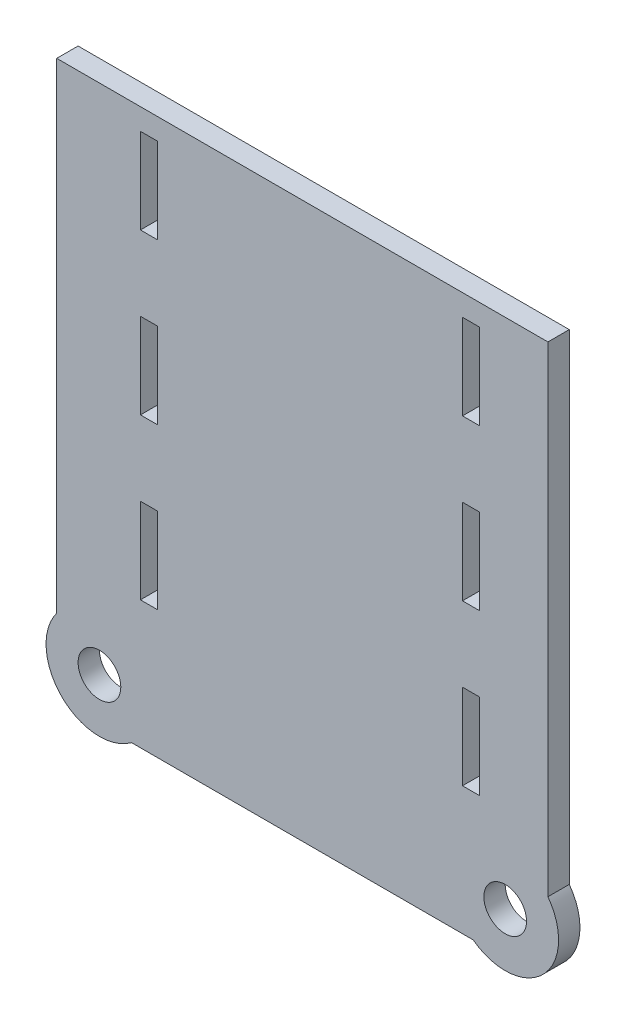
SolidWorks part; units mm, degrees
ref_plane "Front Plane" through (0, 0, 0) normal (0, 0, 1) x (1, 0, 0)
ref_plane "Top Plane" through (0, 0, 0) normal (0, 1, 0) x (1, 0, 0)
ref_plane "Right Plane" through (0, 0, 0) normal (1, 0, 0) x (0, 0, -1)
sketch "Sketch1" plane through (0, 0, 0) normal (0, 0, 1) x (1, 0, 0)
  line L0 (0, 0) -> (0, 152.4) construction
  line L1 (0.0027, -12.7) -> (-50.8, -12.7)
  line L2 (-73.025, 9.525) -> (-73.025, 152.4)
  line L3 (-73.025, 152.4) -> (73.025, 152.4)
  line L4 (73.025, 9.525) -> (73.025, 152.4)
  line L5 (-0.0027, -12.7) -> (50.8, -12.7)
  circle A0 centre (-60.325, 0) radius 6.35
  arc A1 (-73.025, 9.525) -> (-50.8, -12.7) centre (-60.325, 0) ccw
  arc A2 (73.025, 9.525) -> (50.8, -12.7) centre (60.325, 0) cw
  circle A3 centre (60.325, 0) radius 6.35
  dimension "D1" = 12.7
  dimension "D2" = 31.75
  dimension "D3" = 60.325
  dimension "D4" = 146.05
  dimension "D5" = 12.7
  dimension "D6" = 152.4
extrude "Boss-Extrude1" add sketch "Sketch1" along normal mid plane 6.35 contours A2 L4 L3 L2 A1 L1 L5 A0 A3 region at (0, 70.0905, 0)
sketch "Sketch2" plane through (0, 0, 3.175) normal (0, 0, 1) x (1, 0, 0)
  line L0 (-43.053, 152.4) -> (-43.053, -12.7) construction
  line L1 (-73.025, 152.4) -> (73.025, 152.4) construction
  line L2 (50.8, -12.7) -> (-50.8, -12.7) construction
  line L3 (47.625, 152.4) -> (47.625, -12.7) construction
  line L4 (73.025, 9.525) -> (73.025, 152.4) construction
  line L5 (-73.025, 9.525) -> (-73.025, 152.4) construction
  line L6 (-45.593, 120.65) -> (-45.593, 98.425) construction
  line L7 (-48.133, 146.05) -> (-43.053, 146.05)
  line L8 (-48.133, 146.05) -> (-48.133, 120.65)
  line L9 (-48.133, 120.65) -> (-43.053, 120.65)
  line L10 (-43.053, 146.05) -> (-43.053, 120.65)
  line L11 (-48.133, 98.425) -> (-43.053, 98.425)
  line L12 (-48.133, 98.425) -> (-48.133, 73.025)
  line L13 (-48.133, 73.025) -> (-43.053, 73.025)
  line L14 (-43.053, 98.425) -> (-43.053, 73.025)
  line L15 (-48.133, 50.8) -> (-43.053, 50.8)
  line L16 (-48.133, 50.8) -> (-48.133, 25.4)
  line L17 (-48.133, 25.4) -> (-43.053, 25.4)
  line L18 (-43.053, 50.8) -> (-43.053, 25.4)
  line L19 (-45.593, 73.025) -> (-45.593, 50.8) construction
  line L20 (47.625, 120.65) -> (52.705, 120.65)
  line L21 (52.705, 50.8) -> (52.705, 25.4)
  line L22 (47.625, 146.05) -> (52.705, 146.05)
  line L23 (47.625, 73.025) -> (52.705, 73.025)
  line L24 (47.625, 98.425) -> (47.625, 73.025)
  line L25 (47.625, 98.425) -> (52.705, 98.425)
  line L26 (52.705, 152.4) -> (52.705, -13.9266) construction
  line L27 (47.625, 50.8) -> (47.625, 25.4)
  line L28 (47.625, 25.4) -> (52.705, 25.4)
  line L29 (50.165, 120.65) -> (50.165, 98.425) construction
  line L30 (52.705, 98.425) -> (52.705, 73.025)
  line L31 (52.705, 146.05) -> (52.705, 120.65)
  line L32 (47.625, 146.05) -> (47.625, 120.65)
  line L33 (47.625, 50.8) -> (52.705, 50.8)
  line L34 (50.165, 73.025) -> (50.165, 50.8) construction
  arc A0 (50.8, -12.7) -> (73.025, 9.525) centre (60.325, 0) ccw construction
  point P46 (52.4631, 152.4)
  point P47 (21.0966, 148.0911)
  point P48 (0, 0)
  point P49 (52.705, -13.9266)
  point P53 (0, 0)
  dimension "D1" = 25.4
  dimension "D2" = 29.972
  dimension "D3" = 25.4
  dimension "D4" = 5.08
  dimension "D5" = 38.1
  dimension "D6" = 6.35
  dimension "D7" = 5.08
extrude "Cut-Extrude1" cut sketch "Sketch2" against normal through all
